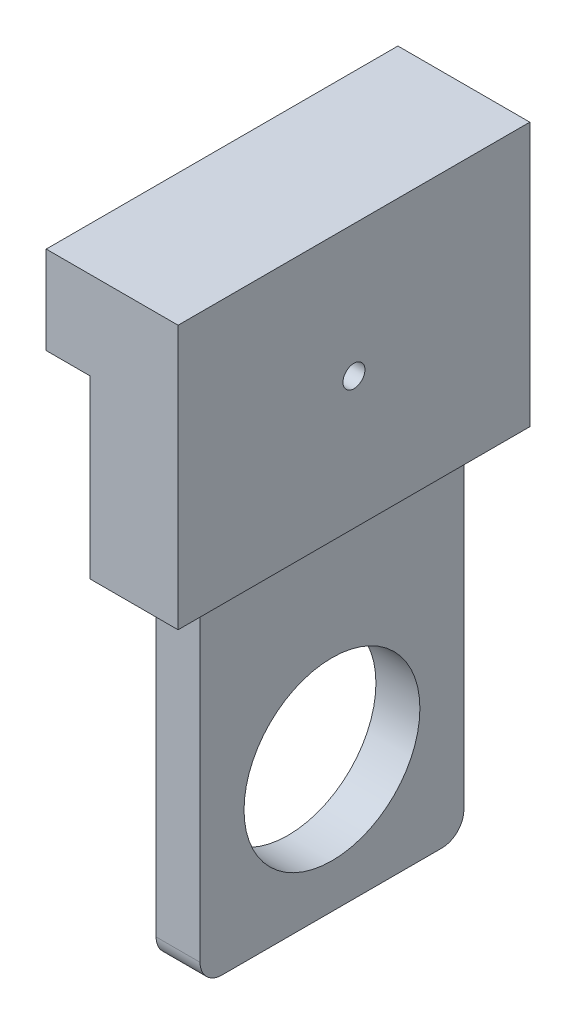
SolidWorks part; units mm, degrees
material "Czyste srebro"
ref_plane "Front Plane" through (0, 0, 0) normal (0, 0, 1) x (1, 0, 0)
ref_plane "Top Plane" through (0, 0, 0) normal (0, 1, 0) x (1, 0, 0)
ref_plane "Right Plane" through (0, 0, 0) normal (1, 0, 0) x (0, 0, -1)
sketch "Szkic1" plane through (0, 0, 0) normal (0, 1, 0) x (1, 0, 0)
  line L1 (-0.5, -2) -> (0.5, -2)
  line L2 (-0.5, -2) -> (-0.5, 2)
  line L3 (-0.5, 2) -> (0.5, 2)
  line L4 (0.5, -2) -> (0.5, 2)
  line L5 (-0.5, -2) -> (0.5, 2) construction
  line L6 (-0.5, 2) -> (0.5, -2) construction
  point P0 (0, 0)
extrude "Dodanie-wyciągnięcie1" add sketch "Szkic1" along normal blind 3 contours L4 L3 L2 L1
sketch "Szkic4" plane through (0, 0, 0) normal (0, -1, 0) x (1, 0, 0)
  line L1 (-0.25, -1.5) -> (0.25, -1.5)
  line L2 (-0.25, -1.5) -> (-0.25, 1.5)
  line L3 (-0.25, 1.5) -> (0.25, 1.5)
  line L4 (0.25, -1.5) -> (0.25, 1.5)
  line L5 (-0.25, -1.5) -> (0.25, 1.5) construction
  line L6 (-0.25, 1.5) -> (0.25, -1.5) construction
  point P0 (0, 0)
extrude "Dodanie-wyciągnięcie3" add sketch "Szkic4" along normal blind 3.9
sketch "Szkic5" plane through (0.25, 0, 0) normal (1, 0, 0) x (0, 0, -1)
  line L0 (0, -3.9) -> (0, -2.4) construction
  line L1 (1.5, -3.9) -> (-1.5, -3.9) construction
  circle A0 centre (0, -2.4) radius 1
extrude "Wytnij-wyciągnięcie2" cut sketch "Szkic5" against normal blind 3.9
fillet "Zaokrąglenie1" radius 0.25 6 edges at (0, -3.9, -1.5) (-0.25, 0, 0) (0, 0, -1.5) (0.25, 0, 0) (0, 0, 1.5) (0, -3.9, 1.5)
sketch "Szkic8" plane through (-0.5, 0, 0) normal (-1, 0, 0) x (0, 0, 1)
  line L0 (2, 3) -> (2, 0) construction
  line L1 (-2, 3) -> (2, 3)
  line L2 (-2, 3) -> (-2, 2)
  line L3 (-2, 2) -> (2, 2)
  line L4 (2, 3) -> (2, 2)
extrude "Dodanie-wyciągnięcie4" add sketch "Szkic8" along normal blind 0.5
sketch "Szkic9" plane through (0.5, 0, 0) normal (1, 0, 0) x (0, 0, -1)
  line L0 (0, 0) -> (0, 1.5) construction
  line L1 (-1.75, 0) -> (1.75, 0) construction
  circle A0 centre (0, 1.5) radius 0.125
extrude "Wytnij-wyciągnięcie3" cut sketch "Szkic9" against normal blind 1
